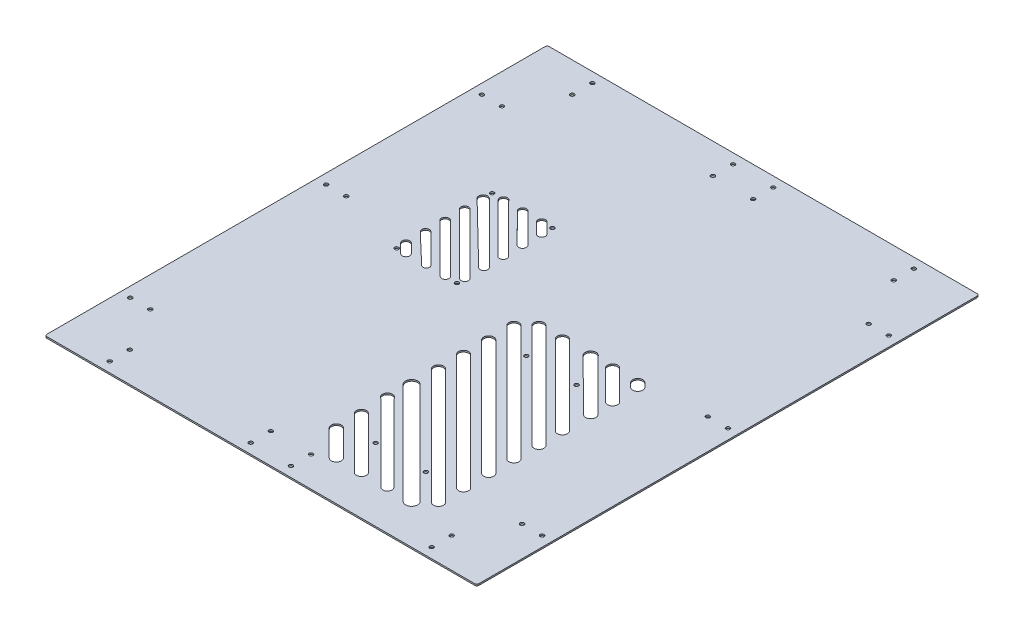
SolidWorks part; units mm, degrees
ref_plane "Front Plane" through (0, 0, 0) normal (0, 0, 1) x (1, 0, 0)
ref_plane "Top Plane" through (0, 0, 0) normal (0, 1, 0) x (1, 0, 0)
ref_plane "Right Plane" through (0, 0, 0) normal (1, 0, 0) x (0, 0, -1)
other "Center of Mass"
sketch "Sketch1" plane through (0, 0, 0) normal (0, 1, 0) x (1, 0, 0)
  line L1 (-215, -250) -> (215, -250)
  line L2 (-215, -250) -> (-215, 250)
  line L3 (-215, 250) -> (215, 250)
  line L4 (215, -250) -> (215, 250)
  line L5 (-215, -250) -> (215, 250) construction
  line L6 (-215, 250) -> (215, -250) construction
  point P0 (0, 0)
  dimension "D1" = 430
  dimension "D2" = 500
extrude "Boss-Extrude1" add sketch "Sketch1" along normal blind 1.5
sketch "Sketch6" plane through (0, 1.5, 0) normal (0, 1, 0) x (1, 0, 0)
  circle A0 centre (92.2927, -28) radius 1.95
  circle A1 centre (42.2927, -28) radius 1.95
  circle A2 centre (92.2927, -178) radius 1.95
  circle A3 centre (42.2927, -178) radius 1.95
  dimension "D1" = 50
  dimension "D2" = 150
sketch "Sketch7" plane through (0, 1.5, 0) normal (0, 1, 0) x (1, 0, 0)
  circle A0 centre (-114.98, 95.1924) radius 1.95
  circle A1 centre (-54.98, 95.1924) radius 1.95
  circle A2 centre (-54.98, 0.1924) radius 1.95
  circle A3 centre (-114.98, 0.1924) radius 1.95
  dimension "D1" = 95
  dimension "D2" = 60
sketch "Sketch12" plane through (0, 0, 0) normal (0, -1, 0) x (-1, 0, 0)
  line L0 (215, -250) -> (-215, -250) construction
  line L1 (-215, 250) -> (215, 250) construction
  line L2 (215, 250) -> (215, -250) construction
  line L3 (-215, -250) -> (-215, 250) construction
  circle A0 centre (-185, -175) radius 1.95
  circle A1 centre (-205, 170) radius 1.95
  circle A3 centre (-185, 10) radius 1.95
  circle A4 centre (-205, 10) radius 1.95
  circle A5 centre (-205, -175) radius 1.95
  circle A6 centre (-185, 170) radius 1.95
  circle A7 centre (205, -175) radius 1.95
  circle A8 centre (205, 20) radius 1.95
  circle A9 centre (185, 175) radius 1.95
  circle A10 centre (205, 175) radius 1.95
  circle A11 centre (185, -175) radius 1.95
  circle A12 centre (185, 20) radius 1.95
  circle A13 centre (160.3499, -240) radius 1.95
  circle A14 centre (160.3499, -220) radius 1.95
  circle A15 centre (20, -240) radius 1.95
  circle A16 centre (20, -220) radius 1.95
  circle A17 centre (-20, -220) radius 1.95
  circle A19 centre (-20, -240) radius 1.95
  circle A20 centre (-160, -240) radius 1.95
  circle A21 centre (-160, -220) radius 1.95
  circle A22 centre (160, 220) radius 1.95
  circle A23 centre (160, 240) radius 1.95
  circle A24 centre (20, 220) radius 1.95
  circle A25 centre (20, 240) radius 1.95
  circle A26 centre (-20, 220) radius 1.95
  circle A27 centre (-20, 240) radius 1.95
  circle A28 centre (-160, 220) radius 1.95
  circle A29 centre (-160, 240) radius 1.95
  dimension "D1" = 10
  dimension "D2" = 20
  dimension "D3" = 10
  dimension "D5" = 10
  dimension "D6" = 20
  dimension "D7" = 20
  dimension "D4" = 20
  dimension "D8" = 10
extrude "Cut-Extrude3" cut sketch "Sketch12" against normal blind 50.8
extrude "Cut-Extrude4" cut sketch "Sketch6" against normal blind 50.8
extrude "Cut-Extrude5" cut sketch "Sketch7" against normal blind 50.8
fillet "Fillet1" radius 2 4 edges at (215, 0.75, -250) (215, 0.75, 250) (-215, 0.75, 250) (-215, 0.75, -250)
sketch "Sketch13" plane through (0, 0, 0) normal (0, -1, 0) x (1, 0, 0)
  line L0 (67.2927, 28) -> (67.2927, 178) construction
  line L6 (92.2927, 178) -> (42.2927, 178) construction
  line L8 (92.2927, 178) -> (92.2927, 28) construction
  line L9 (92.2927, 28) -> (42.2927, 28) construction
  line L10 (42.2927, 178) -> (42.2927, 28) construction
  line L11 (67.2927, 103) -> (42.2927, 103) construction
  line L12 (124.7927, 122.9451) -> (9.7927, 7.9451) construction
  line L13 (124.7927, 210.5) -> (9.7927, 210.5)
  line L14 (124.7927, 210.5) -> (124.7927, -4.5)
  line L15 (124.7927, -4.5) -> (9.7927, -4.5)
  line L16 (9.7927, 210.5) -> (9.7927, -4.5)
  line L17 (124.7927, 210.5) -> (9.7927, -4.5) construction
  line L18 (124.7927, -4.5) -> (9.7927, 210.5) construction
  line L19 (128.3282, 119.4095) -> (13.3282, 4.4095)
  line L20 (121.2572, 126.4806) -> (6.2572, 11.4806)
  line L21 (124.7927, 147.9451) -> (9.7927, 32.9451) construction
  line L22 (128.3282, 144.4095) -> (13.3282, 29.4095)
  line L23 (121.2572, 151.4806) -> (6.2572, 36.4806)
  line L26 (124.7927, 172.9451) -> (9.7927, 57.9451) construction
  line L29 (128.3282, 169.4095) -> (13.3282, 54.4095)
  line L32 (121.2572, 176.4806) -> (6.2572, 61.4806)
  line L35 (124.7927, 197.9451) -> (9.7927, 82.9451) construction
  line L38 (128.3282, 194.4095) -> (13.3282, 79.4095)
  line L41 (121.2572, 201.4806) -> (6.2572, 86.4806)
  line L44 (110.6506, 210.5) -> (9.7927, 109.6421) construction
  line L47 (114.8916, 206.259) -> (14.0337, 105.4011)
  line L50 (102.1686, 210.5) -> (5.5517, 113.8831)
  line L53 (-54.98, -95.1924) -> (-114.98, -95.1924) construction
  line L58 (-114.98, -95.1924) -> (-114.98, -44.2867) construction
  line L62 (86.5307, 210.5) -> (8.6916, 132.661) construction
  line L65 (-114.98, -0.1924) -> (-54.98, -0.1924) construction
  line L66 (-54.98, -0.1924) -> (-54.98, -95.1924) construction
  line L67 (-54.98, -84.5868) -> (-65.5855, -95.1924) construction
  line L68 (-54.98, -89.8901) -> (-60.2822, -95.1924)
  line L69 (-57.6303, -81.9365) -> (-68.2358, -92.5421)
  line L70 (-54.98, -95.1924) -> (-114.98, -0.1924) construction
  line L71 (-54.98, -65.4331) -> (-84.7393, -95.1924) construction
  line L72 (-54.98, -70.7364) -> (-79.4324, -95.1924)
  line L73 (-57.6384, -62.7886) -> (-87.2428, -92.5491)
  line L74 (-54.98, -46.2793) -> (-103.893, -95.1924) construction
  line L75 (-54.98, -51.5826) -> (-98.5897, -95.1924)
  line L76 (-57.6398, -43.6363) -> (-106.2442, -92.5505)
  line L77 (-54.98, -27.1256) -> (-120.2706, -91.5396) construction
  line L78 (-54.98, -32.4289) -> (-111.9255, -89.3745)
  line L79 (-57.5955, -24.4383) -> (-117.9928, -83.2246)
  line L80 (-52.4189, -5.4139) -> (-114.98, -67.9718) construction
  line L81 (-52.3742, -10.6694) -> (-112.3283, -70.6235)
  line L83 (-63.9533, 2.3637) -> (-114.98, -48.8181) construction
  line L84 (-63.9494, -2.7446) -> (-112.3283, -51.1235)
  line L87 (-71.6576, -0.1924) -> (-114.98, -43.5148)
  line L88 (-85.508, -0.1924) -> (-114.98, -29.6644) construction
  line L91 (-83.2026, -2.4978) -> (-112.3283, -31.6235)
  line L92 (-90.2324, -0.1924) -> (-114.98, -23.7903)
  line L93 (-105.7005, -0.1924) -> (-114.98, -10.5106) construction
  line L96 (-103.0489, -2.844) -> (-112.3283, -12.1235)
  line L99 (-111.0038, -0.1924) -> (-114.98, -4.1685)
  line L102 (-60.2822, -95.1924) -> (-62.9366, -97.844)
  line L105 (-98.5897, -95.1924) -> (-100.7736, -97.6705)
  line L106 (-79.4324, -95.1924) -> (-81.8594, -97.7646)
  line L107 (-114.98, -62.6685) -> (-117.6316, -65.3202)
  line L108 (-114.98, -43.5148) -> (-117.4324, -45.635)
  line L109 (-114.98, -4.1685) -> (-117.6316, -6.8202)
  line L110 (-54.98, -89.8901) -> (-52.3283, -87.2358)
  line L111 (-54.98, -70.7364) -> (-52.3283, -68.0843)
  line L112 (-54.98, -51.5826) -> (-52.3283, -48.9306)
  line L113 (-54.98, -32.4289) -> (-52.3283, -29.7772)
  line L114 (-57.5857, -5.4578) -> (-114.98, -62.6685)
  line L115 (-90.2324, -0.1924) -> (-87.7579, 2.1672)
  line L116 (-71.6576, -0.1924) -> (-69.0283, 2.3851)
  line L117 (-111.0038, -0.1924) -> (-108.3522, 2.4593)
  line L118 (-114.98, -23.7903) -> (-117.5678, -26.2579)
  line L119 (89.7127, 207.318) -> (13.4147, 131.0201)
  line L120 (80.1667, 210.5) -> (7.0508, 137.3841)
  line L121 (60.6506, 210.5) -> (9.7927, 159.6421) construction
  line L122 (64.1861, 206.9645) -> (13.3282, 156.1066)
  line L123 (53.5795, 210.5) -> (6.2572, 163.1777)
  line L124 (35.6506, 210.5) -> (9.7927, 184.6421) construction
  line L125 (39.1861, 206.9645) -> (13.3282, 181.1066)
  line L126 (28.5795, 210.5) -> (6.2572, 188.1777)
  line L127 (10.6506, 210.5) -> (9.7927, 209.6421) construction
  line L128 (16.6674, 209.4458) -> (13.3282, 206.1066)
  line L130 (128.3284, -3.8936) -> (124.1859, -8.0357)
  line L133 (125.6429, 98.792) -> (22.3509, -4.5) construction
  line L134 (129.1784, 95.2564) -> (29.422, -4.5)
  line L135 (122.1073, 102.3275) -> (18.8154, -0.9645)
  line L136 (124.7927, 74.6421) -> (45.6506, -4.5) construction
  line L137 (128.3282, 71.1066) -> (52.7216, -4.5)
  line L138 (121.2572, 78.1777) -> (42.115, -0.9645)
  line L139 (124.7927, 46.436) -> (73.8567, -4.5) construction
  line L140 (128.4341, 42.7783) -> (80.9436, -4.5)
  line L141 (121.1513, 50.0937) -> (70.1015, -0.728)
  line L142 (124.7927, 24.6421) -> (95.6506, -4.5) construction
  line L143 (128.3282, 21.1066) -> (102.7216, -4.5)
  line L144 (121.2572, 28.1777) -> (92.115, -0.9645)
  line L145 (124.7928, -0.358) -> (120.6506, -4.5) construction
  line L147 (121.2572, 3.1777) -> (117.115, -0.9645)
  line L166 (6.6802, 213.5553) -> (10.376, 216.4949)
  line L167 (28.5795, 210.5) -> (32.115, 214.0355)
  line L168 (53.5795, 210.5) -> (57.115, 214.0355)
  line L169 (80.1667, 210.5) -> (83.3487, 213.682)
  line L170 (102.1686, 210.5) -> (106.4096, 214.741)
  line L171 (102.7216, -4.5) -> (99.1861, -8.0355)
  line L172 (80.9436, -4.5) -> (77.854, -8.0143)
  line L173 (52.7216, -4.5) -> (49.1861, -8.0355)
  line L174 (29.422, -4.5) -> (25.8864, -8.0355)
  line L356 (124.7927, 347.9451) -> (9.7927, 232.9451) construction
  line L357 (128.3282, 344.4095) -> (13.3282, 229.4095) [skipped]
  line L358 (121.2572, 351.4806) -> (6.2572, 236.4806) [skipped]
  line L359 (124.7927, 322.9451) -> (9.7927, 207.9451) construction
  line L360 (128.3282, 319.4095) -> (13.3282, 204.4095) [skipped]
  line L361 (121.2572, 326.4806) -> (6.2572, 211.4806) [skipped]
  line L362 (124.7927, 297.9451) -> (9.7927, 182.9451) construction
  line L363 (128.3282, 294.4095) -> (13.3282, 179.4095) [skipped]
  line L364 (121.2572, 301.4806) -> (6.2572, 186.4806) [skipped]
  line L365 (124.7927, 272.9451) -> (9.7927, 157.9451) construction
  line L366 (128.3282, 269.4095) -> (13.3282, 154.4095) [skipped]
  line L367 (121.2572, 276.4806) -> (6.2572, 161.4806) [skipped]
  line L368 (124.7927, 247.9451) -> (9.7927, 132.9451) construction
  line L369 (128.3282, 244.4095) -> (13.3282, 129.4095) [skipped]
  line L370 (121.2572, 251.4806) -> (6.2572, 136.4806) [skipped]
  line L371 (124.7927, 222.9451) -> (9.7927, 107.9451) construction
  line L372 (128.3282, 219.4095) -> (13.3282, 104.4095) [skipped]
  line L373 (121.2572, 226.4806) -> (6.2572, 111.4806) [skipped]
  line L374 (124.7927, 347.9451) -> (9.7927, 232.9451) construction
  line L375 (128.3282, 344.4095) -> (13.3282, 229.4095) [skipped]
  line L376 (121.2572, 351.4806) -> (6.2572, 236.4806) [skipped]
  line L377 (124.7927, 322.9451) -> (9.7927, 207.9451) construction
  line L378 (128.3282, 319.4095) -> (13.3282, 204.4095) [skipped]
  line L379 (121.2572, 326.4806) -> (6.2572, 211.4806) [skipped]
  line L380 (124.7927, 297.9451) -> (9.7927, 182.9451) construction
  line L381 (128.3282, 294.4095) -> (13.3282, 179.4095) [skipped]
  line L382 (121.2572, 301.4806) -> (6.2572, 186.4806) [skipped]
  line L383 (124.7927, 272.9451) -> (9.7927, 157.9451) construction
  line L384 (128.3282, 269.4095) -> (13.3282, 154.4095) [skipped]
  line L385 (121.2572, 276.4806) -> (6.2572, 161.4806) [skipped]
  line L386 (124.7927, 247.9451) -> (9.7927, 132.9451) construction
  line L387 (128.3282, 244.4095) -> (13.3282, 129.4095) [skipped]
  line L388 (121.2572, 251.4806) -> (6.2572, 136.4806) [skipped]
  line L389 (124.7927, 222.9451) -> (9.7927, 107.9451) construction
  line L390 (128.3282, 219.4095) -> (13.3282, 104.4095) [skipped]
  line L391 (121.2572, 226.4806) -> (6.2572, 111.4806) [skipped]
  arc A32 (128.3282, 119.4095) -> (121.2572, 126.4806) centre (124.7927, 122.9451) ccw
  arc A59 (-68.2358, -92.5421) -> (-62.9366, -97.844) centre (-65.5855, -95.1924) ccw
  arc A60 (-87.2428, -92.5491) -> (-81.8594, -97.7646) centre (-84.5855, -95.1924) ccw
  arc A61 (-106.2442, -92.5505) -> (-100.7736, -97.6705) centre (-103.5855, -95.1924) ccw
  arc A63 (-117.6316, -65.3202) -> (-112.3283, -70.6235) centre (-114.98, -67.9718) ccw
  arc A64 (-117.4324, -45.635) -> (-112.3283, -51.1235) centre (-114.98, -48.4718) ccw
  arc A65 (-117.5678, -26.2579) -> (-112.3283, -31.6235) centre (-114.98, -28.9718) ccw
  arc A66 (-117.6316, -6.8202) -> (-112.3283, -12.1235) centre (-114.98, -9.4718) ccw
  arc A67 (-52.3283, -29.7772) -> (-57.5955, -24.4383) centre (-54.98, -27.1256) ccw
  arc A68 (-52.3283, -48.9306) -> (-57.6398, -43.6363) centre (-54.98, -46.2793) ccw
  arc A69 (-52.3283, -68.0843) -> (-57.6384, -62.7886) centre (-54.98, -65.4331) ccw
  arc A70 (-52.3283, -87.2358) -> (-57.6303, -81.9365) centre (-54.98, -84.5868) ccw
  arc A71 (-52.3742, -10.6694) -> (-57.5857, -5.4578) centre (-54.98, -8.0636) ccw
  arc A72 (-117.9928, -83.2246) -> (-111.9255, -89.3745) centre (-114.98, -86.32) ccw
  arc A73 (6.2572, 11.4806) -> (13.3282, 4.4095) centre (9.7927, 7.9451) ccw
  arc A74 (128.3282, 144.4095) -> (121.2572, 151.4806) centre (124.7927, 147.9451) ccw
  arc A75 (6.2572, 36.4806) -> (13.3282, 29.4095) centre (9.7927, 32.9451) ccw
  arc A76 (128.3282, 169.4095) -> (121.2572, 176.4806) centre (124.7927, 172.9451) ccw
  arc A77 (6.2572, 61.4806) -> (13.3282, 54.4095) centre (9.7927, 57.9451) ccw
  circle A78 centre (-122.5855, -95.1924) radius 3.7481 [skipped]
  arc A79 (-83.2026, -2.4978) -> (-87.7579, 2.1672) centre (-85.508, -0.1924) ccw
  arc A80 (-103.0489, -2.844) -> (-108.3522, 2.4593) centre (-105.7005, -0.1924) ccw
  arc A81 (-63.9494, -2.7446) -> (-69.0283, 2.3851) centre (-66.5016, -0.1924) ccw
  arc A82 (128.3282, 194.4095) -> (121.2572, 201.4806) centre (124.7927, 197.9451) ccw
  arc A83 (6.2572, 86.4806) -> (13.3282, 79.4095) centre (9.7927, 82.9451) ccw
  arc A85 (5.5517, 113.8831) -> (14.0337, 105.4011) centre (9.7927, 109.6421) ccw
  arc A87 (7.0508, 137.3841) -> (13.4147, 131.0201) centre (8.6916, 132.661) ccw
  arc A89 (6.2572, 163.1777) -> (13.3282, 156.1066) centre (9.7927, 159.6421) ccw
  arc A91 (6.2572, 188.1777) -> (13.3282, 181.1066) centre (9.7927, 184.6421) ccw
  arc A93 (6.6802, 213.5553) -> (13.3282, 206.1066) centre (9.7927, 209.6421) ccw
  arc A96 (129.1784, 95.2564) -> (122.1073, 102.3275) centre (125.6429, 98.792) ccw
  arc A98 (128.3282, 71.1066) -> (121.2572, 78.1777) centre (124.7927, 74.6421) ccw
  arc A100 (128.4341, 42.7783) -> (121.1513, 50.0937) centre (124.7927, 46.436) ccw
  arc A102 (128.3282, 21.1066) -> (121.2572, 28.1777) centre (124.7927, 24.6421) ccw
  arc A104 (128.3284, -3.8936) -> (121.2572, 3.1777) centre (124.7928, -0.358) ccw
  arc A118 (117.115, -0.9645) -> (124.1859, -8.0357) centre (120.6506, -4.5) ccw
  arc A119 (92.115, -0.9645) -> (99.1861, -8.0355) centre (95.6506, -4.5) ccw
  arc A120 (70.1015, -0.728) -> (77.854, -8.0143) centre (73.8567, -4.5) ccw
  arc A121 (42.115, -0.9645) -> (49.1861, -8.0355) centre (45.6506, -4.5) ccw
  arc A122 (18.8154, -0.9645) -> (25.8864, -8.0355) centre (22.3509, -4.5) ccw
  arc A123 (114.8916, 206.259) -> (106.4096, 214.741) centre (110.6506, 210.5) ccw
  arc A124 (89.7127, 207.318) -> (83.3487, 213.682) centre (86.5307, 210.5) ccw
  arc A125 (64.1861, 206.9645) -> (57.115, 214.0355) centre (60.6506, 210.5) ccw
  arc A126 (39.1861, 206.9645) -> (32.115, 214.0355) centre (35.6506, 210.5) ccw
  arc A127 (16.6674, 209.4458) -> (10.376, 216.4949) centre (13.3216, 212.7917) ccw
  arc A261 (128.3282, 344.4095) -> (121.2572, 351.4806) centre (124.7927, 347.9451) ccw [skipped]
  arc A262 (6.2572, 236.4806) -> (13.3282, 229.4095) centre (9.7927, 232.9451) ccw [skipped]
  arc A263 (128.3282, 319.4095) -> (121.2572, 326.4806) centre (124.7927, 322.9451) ccw [skipped]
  arc A264 (6.2572, 211.4806) -> (13.3282, 204.4095) centre (9.7927, 207.9451) ccw [skipped]
  arc A265 (128.3282, 294.4095) -> (121.2572, 301.4806) centre (124.7927, 297.9451) ccw [skipped]
  arc A266 (6.2572, 186.4806) -> (13.3282, 179.4095) centre (9.7927, 182.9451) ccw [skipped]
  arc A267 (128.3282, 269.4095) -> (121.2572, 276.4806) centre (124.7927, 272.9451) ccw [skipped]
  arc A268 (6.2572, 161.4806) -> (13.3282, 154.4095) centre (9.7927, 157.9451) ccw [skipped]
  arc A269 (128.3282, 244.4095) -> (121.2572, 251.4806) centre (124.7927, 247.9451) ccw [skipped]
  arc A270 (6.2572, 136.4806) -> (13.3282, 129.4095) centre (9.7927, 132.9451) ccw [skipped]
  arc A271 (128.3282, 219.4095) -> (121.2572, 226.4806) centre (124.7927, 222.9451) ccw [skipped]
  arc A272 (6.2572, 111.4806) -> (13.3282, 104.4095) centre (9.7927, 107.9451) ccw [skipped]
  point P18 (67.2927, 65.4451)
  point P23 (67.2927, 90.4451)
  point P30 (67.2927, 115.4451)
  point P37 (67.2927, 140.4451)
  point P46 (67.2927, 167.1421)
  point P54 (67.2927, 192.1421)
  point P73 (67.2927, 217.1421)
  point P85 (67.2927, 153)
  point P89 (-59.0853, -88.6922)
  point P94 (67.2927, 42.1421)
  point P102 (67.2927, 17.1421)
  point P116 (67.2927, 193)
  point P124 (-66.4512, -76.9043)
  point P125 (67.2927, 173)
  point P135 (-73.8171, -65.1165)
  point P151 (-81.183, -53.3286)
  point P153 (67.2927, 193)
  point P156 (67.2927, 292.1421)
  point P159 (-88.5489, -41.5407)
  point P160 (67.2927, 173)
  point P167 (67.2927, 153)
  point P168 (-95.9147, -29.7529)
  point P174 (67.2927, 193)
  point P176 (-103.2806, -17.965)
  point P181 (67.2927, 173)
  point P184 (-110.6465, -6.1771)
  point P188 (67.2927, 153)
  point P207 (67.2927, 267.1421)
  point P227 (67.2927, 242.1421)
  point P235 (67.2927, 192.1421)
  point P242 (67.2927, 167.1421)
  point P251 (67.2927, 193)
  point P258 (67.2927, 173)
  point P265 (67.2927, 153)
  point P272 (67.2927, 193)
  point P279 (67.2927, 173)
  point P286 (67.2927, 153)
  point P321 (67.2927, 193)
  point P328 (67.2927, 173)
  point P335 (67.2927, 153)
  point P342 (67.2927, 193)
  point P349 (67.2927, 173)
  point P356 (67.2927, 153)
  point P365 (67.2927, 193)
  point P372 (67.2927, 173)
  point P379 (67.2927, 153)
  point P386 (67.2927, 193)
  point P393 (67.2927, 173)
  point P400 (67.2927, 153)
  point P407 (67.2927, 193)
  point P414 (67.2927, 173)
  point P421 (67.2927, 153)
  point P428 (67.2927, 193)
  point P435 (67.2927, 173)
  point P442 (67.2927, 153)
  point P449 (67.2927, 193)
  point P456 (67.2927, 173)
  point P463 (67.2927, 153)
  point P470 (67.2927, 193)
  point P477 (67.2927, 173)
  point P484 (67.2927, 153)
  point P491 (67.2927, 193)
  point P498 (67.2927, 173)
  point P505 (67.2927, 153)
  point P512 (67.2927, 193)
  point P519 (67.2927, 173)
  point P526 (67.2927, 153)
  point P533 (67.2927, 193)
  point P540 (67.2927, 173)
  point P547 (67.2927, 153)
  point P554 (67.2927, 193)
  point P561 (67.2927, 173)
  point P568 (67.2927, 153)
  point P575 (67.2927, 193)
  point P582 (67.2927, 173)
  point P589 (67.2927, 153)
  point P596 (67.2927, 193)
  point P603 (67.2927, 173)
  point P610 (67.2927, 153)
  point P617 (67.2927, 193)
  point P624 (67.2927, 173)
  point P631 (67.2927, 153)
  point P638 (67.2927, 193)
  point P645 (67.2927, 173)
  point P652 (67.2927, 153)
  point P677 (67.2927, 292.1421)
  point P684 (67.2927, 267.1421)
  point P691 (67.2927, 242.1421)
  point P698 (67.2927, 217.1421)
  point P705 (67.2927, 192.1421)
  point P712 (67.2927, 167.1421)
  point P719 (67.2927, 288.6066)
  point P726 (67.2927, 263.6066)
  point P733 (67.2927, 238.6066)
  point P740 (67.2927, 213.6066)
  point P747 (67.2927, 188.6066)
  point P754 (67.2927, 163.6066)
  point P761 (67.2927, 288.6066)
  point P768 (67.2927, 263.6066)
  point P775 (67.2927, 238.6066)
  point P782 (67.2927, 213.6066)
  point P789 (67.2927, 188.6066)
  point P796 (67.2927, 163.6066)
  point P803 (67.2927, 288.6066)
  point P810 (67.2927, 263.6066)
  point P817 (67.2927, 238.6066)
  point P824 (67.2927, 213.6066)
  point P831 (67.2927, 188.6066)
  point P838 (67.2927, 163.6066)
  point P845 (67.2927, 288.6066)
  point P852 (67.2927, 263.6066)
  point P859 (67.2927, 238.6066)
  point P866 (67.2927, 213.6066)
  point P873 (67.2927, 188.6066)
  point P880 (67.2927, 163.6066)
  point P887 (67.2927, 288.6066)
  point P894 (67.2927, 263.6066)
  point P901 (67.2927, 238.6066)
  point P908 (67.2927, 213.6066)
  point P915 (67.2927, 188.6066)
  point P922 (67.2927, 163.6066)
  point P929 (67.2927, 288.6066)
  point P936 (67.2927, 263.6066)
  point P943 (67.2927, 238.6066)
  point P950 (67.2927, 213.6066)
  point P957 (67.2927, 188.6066)
  point P964 (67.2927, 163.6066)
  point P971 (67.2927, 289.3137)
  point P978 (67.2927, 264.3137)
  point P985 (67.2927, 239.3137)
  point P992 (67.2927, 214.3137)
  point P999 (67.2927, 189.3137)
  point P1006 (67.2927, 164.3137)
  point P1013 (67.2927, 289.3137)
  point P1020 (67.2927, 264.3137)
  point P1027 (67.2927, 239.3137)
  point P1034 (67.2927, 214.3137)
  point P1041 (67.2927, 189.3137)
  point P1048 (67.2927, 164.3137)
  point P1055 (67.2927, 290.4451)
  point P1062 (67.2927, 265.4451)
  point P1069 (67.2927, 240.4451)
  point P1076 (67.2927, 215.4451)
  point P1083 (67.2927, 190.4451)
  point P1090 (67.2927, 165.4451)
  point P1097 (67.2927, 290.4451)
  point P1104 (67.2927, 265.4451)
  point P1111 (67.2927, 240.4451)
  point P1118 (67.2927, 215.4451)
  point P1125 (67.2927, 190.4451)
  point P1132 (67.2927, 165.4451)
  point P1139 (67.2927, 290.4451)
  point P1146 (67.2927, 265.4451)
  point P1153 (67.2927, 240.4451)
  point P1160 (67.2927, 215.4451)
  point P1167 (67.2927, 190.4451)
  point P1174 (67.2927, 165.4451)
  dimension "D1" = 115
  dimension "D5" = 45
  dimension "D6" = 4
  dimension "D7" = 4
  dimension "D8" = 45
  dimension "D9" = 3.8
  dimension "D10" = 10
  dimension "D2" = 215
  dimension "D3" = 45
  dimension "D4" = 5
  dimension "D11" = 7.68
  dimension "D12" = 10
  dimension "D13" = 9
  dimension "D14" = 45
  dimension "D15" = 45
  dimension "D16" = 5
  dimension "D17" = 3.8
extrude "Cut-Extrude6" cut sketch "Sketch13" against normal blind 10 contours L69 A59 L102 L68 L110 A70 | A69 L73 A60 L106 L72 L111 | L75 L105 A61 L76 A68 L112 | A67 L79 A72 L78 L113 | L81 A63 L107 L114 A71 | L108 A64 L84 A81 L116 L87 | A65 L91 A79 L115 L92 L118 | L96 A66 L109 L99 L117 A80 | A125 L168 L123 A89 L122 | A126 L167 L126 A91 L125 | L119 A87 L120 L169 A124 | A123 L170 L50 A85 L47 | L38 A83 L41 A82 | L29 A77 L32 A76 | L22 A75 L23 A74 | L20 A73 L19 A32 | L135 A122 L174 L134 A96 | L138 A121 L173 L137 A98 | L141 A120 L172 L140 A100 | L144 A119 L171 L143 A102 | L147 A118 L130 A104
